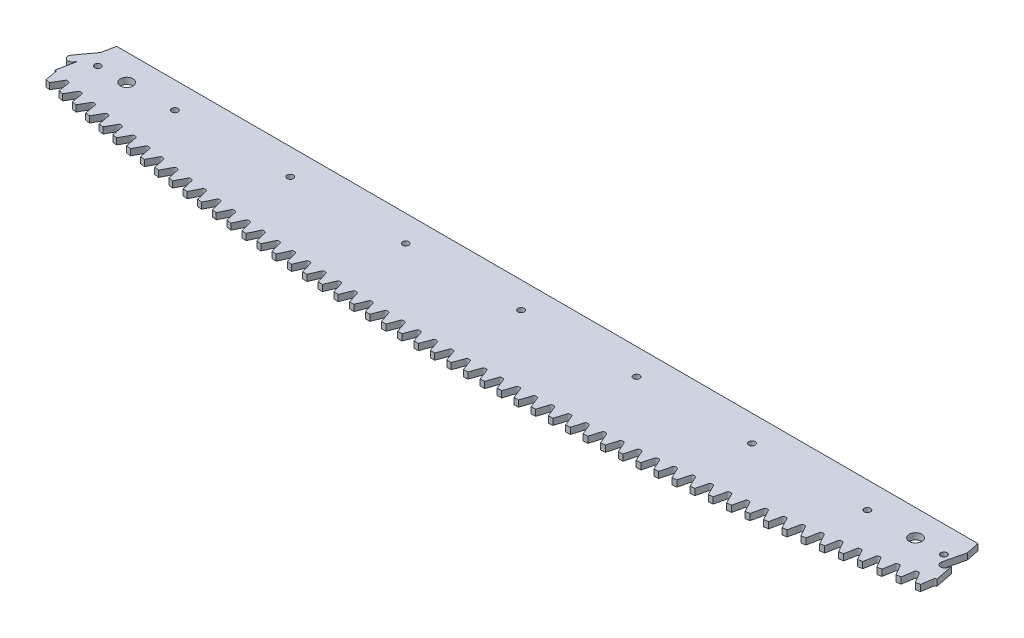
SolidWorks part; units mm, degrees
note: '?' marks a value the reader was unsure of.
ref_plane "Front Plane" through (0, 0, 0) normal (0, 0, 1) x (1, 0, 0)
ref_plane "Top Plane" through (0, 0, 0) normal (0, 1, 0) x (1, 0, 0)
ref_plane "Right Plane" through (0, 0, 0) normal (1, 0, 0) x (0, 0, -1)
sketch "Sketch1" plane through (0, 0, 0) normal (0, 1, 0) x (1, 0, 0)
  line L0 (0, 0) -> (0, -2165) construction
  line L1 (0, 0) -> (-422.3705, -2123.4001) construction
  line L2 (0, 0) -> (422.3705, -2123.4001) construction
  line L3 (-394.8962, -2113.4231) -> (394.8962, -2113.4231) construction
  line L4 (-394.8962, -2088.4231) -> (394.8962, -2088.4231) construction
  line L5 (-410.4404, -2063.4231) -> (410.4404, -2063.4231)
  line L7 (410.4404, -2063.4231) -> (422.3705, -2123.4001)
  line L8 (-410.4404, -2063.4231) -> (-422.3705, -2123.4001)
  line L9 (24.5196, -4.8773) -> (-397.8509, -2128.2774) construction
  line L10 (-24.5196, -4.8773) -> (397.8509, -2128.2774) construction
  line L11 (0, -2088.4231) -> (110, -2088.4231) construction
  line L12 (0, -2088.4231) -> (-110, -2088.4231) construction
  arc A0 (-422.3705, -2123.4001) -> (422.3705, -2123.4001) centre (0, 0) ccw
  circle A1 centre (0, 0) radius 2150 construction
  circle A2 centre (-375.9346, -2088.4231) radius 6
  circle A3 centre (375.9346, -2088.4231) radius 6
  circle A4 centre (0, -2088.4231) radius 3
  circle A5 centre (110, -2088.4231) radius 3
  circle A6 centre (220, -2088.4231) radius 3
  circle A7 centre (330, -2088.4231) radius 3
  circle A8 centre (-110, -2088.4231) radius 3
  circle A9 centre (-220, -2088.4231) radius 3
  circle A10 centre (-330, -2088.4231) radius 3
  circle A11 centre (-403.2198, -2088.633) radius 3
  circle A12 centre (403.2198, -2088.633) radius 3
  dimension "D3" = 4300
  dimension "D8" = 12
  dimension "D10" = 6
  dimension "D15" = 12
  dimension "D1" = 2165
  dimension "D2" = 22.5
  dimension "D4" = 50
  dimension "D5" = 25
  dimension "D6" = 25
  dimension "D7" = 25
  dimension "D9" = 13.72
  dimension "D12" = 110
  dimension "D14" = 110
  dimension "D11" = 4
  dimension "D13" = 4
extrude "Boss-Extrude1" add sketch "Sketch1" along normal blind 6
sketch "Sketch4" plane through (0, 6, 0) normal (0, 1, 0) x (1, 0, 0)
  line L0 (0, -2165) -> (0, -2153.75) construction
  arc A0 (5.7759, -2164.9923) -> (-5.7759, -2164.9923) centre (0, 0) cw
  spline S0 degree 3 poles (5.7759, -2164.9923) (5.6741, -2164.72) (5.5062, -2164.2705) (5.2728, -2163.6438) (5.0755, -2163.1128) (4.879, -2162.5828) (4.6834, -2162.0537) (4.4885, -2161.5255) (4.2944, -2160.9983) (4.1012, -2160.472) (3.9087, -2159.9467) (3.717, -2159.4223) (3.5261, -2158.8988) (3.3361, -2158.3763) (3.1468, -2157.8548) (2.9583, -2157.3342) (2.7704, -2156.8146) (2.5842, -2156.2957) (2.3326, -2155.6065) (2.1391, -2155.011) (1.9388, -2154.5303) (1.8119, -2154.3372) (1.6589, -2154.1649) (1.4808, -2154.0182) (1.2826, -2153.9002) (1.0687, -2153.8144) (0.8441, -2153.7605) (0.4858, -2153.7412) (0, -2153.7564) (-0.4858, -2153.7412) (-0.8441, -2153.7605) (-1.0687, -2153.8144) (-1.2826, -2153.9002) (-1.4808, -2154.0182) (-1.6589, -2154.1649) (-1.8119, -2154.3372) (-1.9388, -2154.5303) (-2.1391, -2155.011) (-2.3326, -2155.6065) (-2.5842, -2156.2957) (-2.7704, -2156.8146) (-2.9583, -2157.3342) (-3.1468, -2157.8548) (-3.3361, -2158.3763) (-3.5261, -2158.8988) (-3.717, -2159.4223) (-3.9087, -2159.9467) (-4.1012, -2160.472) (-4.2944, -2160.9983) (-4.4885, -2161.5255) (-4.6834, -2162.0537) (-4.879, -2162.5828) (-5.0755, -2163.1128) (-5.2728, -2163.6438) (-5.5062, -2164.2705) (-5.6741, -2164.72) (-5.7759, -2164.9923) knots 0.009781 0.009781 0.009781 0.009781 0.041766 0.062585 0.083361 0.104095 0.124786 0.145434 0.16604 0.186603 0.207124 0.227602 0.248037 0.26843 0.28878 0.309088 0.329352 0.349575 0.369754 0.410065 0.418491 0.426918 0.435344 0.44377 0.452197 0.460623 0.46905 0.477476 0.5 0.522524 0.53095 0.539377 0.547803 0.55623 0.564656 0.573082 0.581509 0.589935 0.630246 0.650425 0.670648 0.690912 0.71122 0.73157 0.751963 0.772398 0.792876 0.813397 0.83396 0.854566 0.875214 0.895905 0.916639 0.937415 0.958234 0.990219 0.990219 0.990219 0.990219
  dimension "D1" = 2165
extrude "Cut-Extrude1" cut sketch "Sketch4" against normal up to surface (6 mm away) up to face at (0, 0, 2103.8116)
ref_axis "Axis1" through (0, 6.3, 0) along (0, -1, 0)?
pattern_circular "CirPattern1" count 28 every 0.417 about axis through (0, 6.3, 0) along (0, -1, 0) of "Cut-Extrude1"
sketch "Sketch5" plane through (0, 6, 0) normal (0, 1, 0) x (1, 0, 0)
  line L0 (412.9765, -2076.1733) -> (408.2228, -2095.6001)
  line L1 (408.2228, -2095.6001) -> (415.9936, -2097.5016) construction
  line L2 (415.9936, -2097.5016) -> (416.6695, -2094.7391)
  line L6 (420.1758, -2112.3663) -> (410.4404, -2063.4231) construction
  line L8 (412.9765, -2076.1733) -> (416.6695, -2094.7391)
  arc A0 (408.2228, -2095.6001) -> (415.9936, -2097.5016) centre (412.1082, -2096.5508) ccw
  dimension "D1" = 25
  dimension "D2" = 13
  dimension "D3" = 20
  dimension "D4" = 8
extrude "Cut-Extrude2" cut sketch "Sketch5" against normal up to surface (6 mm away) up to face at (-2.7474, 0, 2148.8617)
sketch "Sketch7" plane through (0, 6, 0) normal (0, 1, 0) x (1, 0, 0)
  line L0 (-412.9765, -2076.1733) -> (-424.8027, -2092.3022)
  line L1 (-410.4404, -2063.4231) -> (-420.1758, -2112.3663) construction
  line L2 (-424.8027, -2092.3022) -> (-418.3512, -2097.0326) construction
  line L6 (-418.3512, -2097.0326) -> (-416.6695, -2094.7391)
  line L7 (-416.6695, -2094.7391) -> (-412.9765, -2076.1733)
  arc A1 (-424.8027, -2092.3022) -> (-418.3512, -2097.0326) centre (-421.577, -2094.6674) ccw
  dimension "D1" = 13
  dimension "D2" = 25
  dimension "D3" = 20
  dimension "D4" = 8
extrude "Boss-Extrude4" add sketch "Sketch7" against normal up to surface (6 mm away) up to face at (11.5966, 0, 2146.9001)
